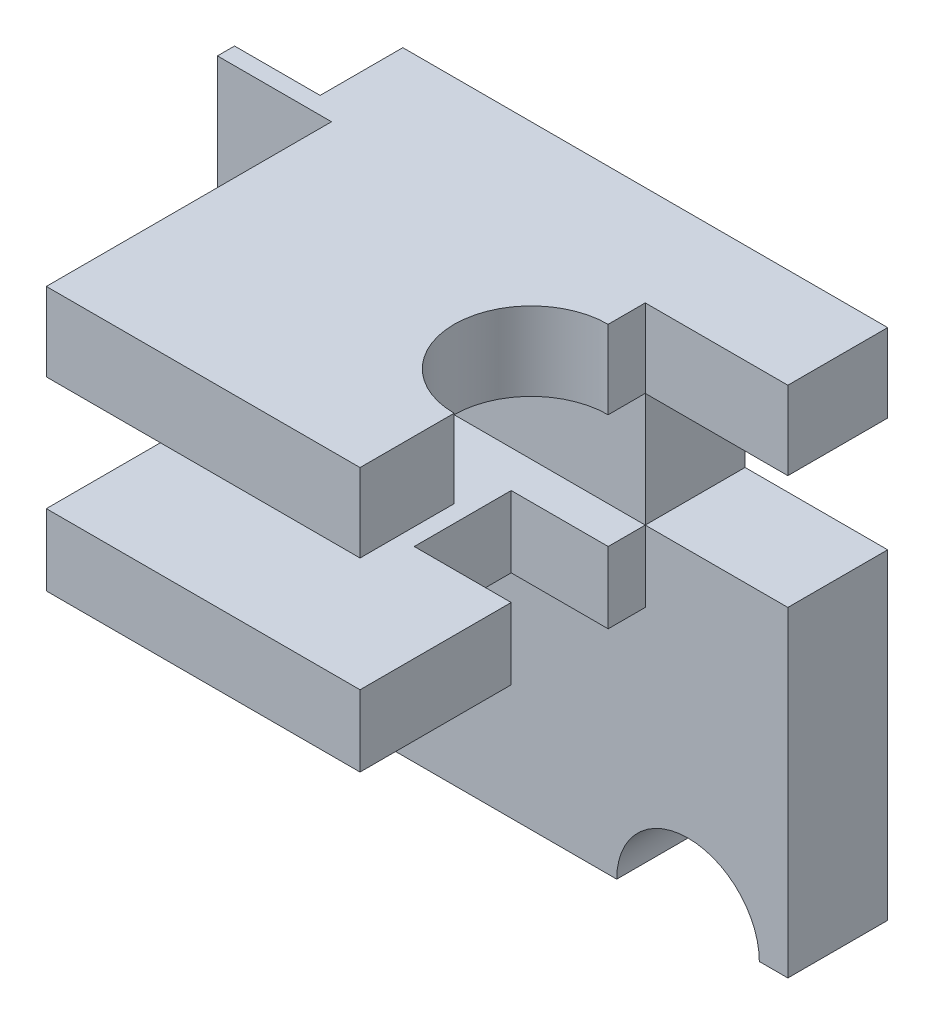
SolidWorks part; units mm, degrees
ref_plane "Спереди" through (0, 0, 0) normal (0, 0, 1) x (1, 0, 0)
ref_plane "Сверху" through (0, 0, 0) normal (0, 1, 0) x (1, 0, 0)
ref_plane "Справа" through (0, 0, 0) normal (1, 0, 0) x (0, 0, -1)
sketch "Эскиз1" plane through (0, 0, 0) normal (0, 0, 1) x (1, 0, 0)
  line L0 (40, -90) -> (90, -90)
  line L1 (-100, -90) -> (100, -90)
  line L2 (-100, -90) -> (-100, 90)
  line L3 (-100, 90) -> (100, 90)
  line L4 (100, -90) -> (100, 90)
  line L5 (-100, -90) -> (100, 90) construction
  line L6 (-100, 90) -> (100, -90) construction
  line L7 (100, 62.5253) -> (50, 62.5253)
  line L8 (100, 62.5253) -> (100, 22.5253)
  line L9 (100, 22.5253) -> (50, 22.5253)
  line L10 (50, 62.5253) -> (50, 22.5253)
  arc A0 (40, -90) -> (90, -90) centre (65, -90) cw
  point P0 (0, 0)
  dimension "D6" = 25
  dimension "D1" = 200
  dimension "D2" = 180
  dimension "D3" = 50
  dimension "D4" = 40
  dimension "D5" = 22.5253
  dimension "D7" = 35
extrude "Бобышка-Вытянуть3" add sketch "Эскиз1" along normal blind 35 contours L2 L1 L4 L3
extrude "Вырез-Вытянуть2" cut sketch "Эскиз1<3>" along normal through all contours A0 L0 | L9 L10 L7 L8 region at (65, -79.3897, 0)
sketch "Эскиз1<3>" plane through (0, 0, 0) normal (0, 0, 1) x (1, 0, 0) same geometry as "Эскиз1"
sketch "Эскиз4" plane through (0, 90, 0) normal (0, 1, 0) x (1, 0, 0)
  line L0 (-100, -35) -> (100, -35) construction
  line L1 (50, -35) -> (-60, -35)
  line L2 (50, -35) -> (50, -135)
  line L3 (50, -135) -> (-60, -135)
  line L4 (-60, -35) -> (-60, -135)
  line L5 (100, -35) -> (100, 0) construction
  dimension "D1" = 50
  dimension "D2" = 110
  dimension "D3" = 100
extrude "Бобышка-Вытянуть4" add sketch "Эскиз4" against normal up to surface (27.4747 mm away) contours L2 L1 L4 L3 up to face at (75, 62.5253, 17.5)
sketch "Эскиз5" plane through (0, 90, 0) normal (0, 1, 0) x (1, 0, 0)
sketch "Эскиз6" plane through (0, 90, 0) normal (0, 1, 0) x (1, 0, 0)
extrude "Бобышка-Вытянуть5" add sketch "Эскиз4<4>" against normal blind 25 from surface starting at face at (75, 22.5253, 17.5)
sketch "Эскиз4<4>" plane through (0, 90, 0) normal (0, 1, 0) x (1, 0, 0) same geometry as "Эскиз4"
sketch "Эскиз9" plane through (0, 90, 0) normal (0, 1, 0) x (1, 0, 0)
  line L1 (-100, 0) -> (-70, 0)
  line L2 (-100, 0) -> (-100, -29)
  line L3 (-100, -29) -> (-70, -29)
  line L4 (-70, 0) -> (-70, -29)
  dimension "D1" = 29
  dimension "D2" = 30
extrude "Вырез-Вытянуть5" cut sketch "Эскиз9" against normal through all
sketch "Эскиз10" plane through (0, 90, 0) normal (0, 1, 0) x (1, 0, 0)
  line L0 (50, -35) -> (50, -135) construction
  line L1 (50, -35) -> (100, -35) construction
  line L2 (50, -48) -> (50, -102)
  arc A0 (50, -48) -> (50, -102) centre (50, -75) ccw
  dimension "D1" = 13
  dimension "D2" = 27
extrude "Вырез-Вытянуть6" cut sketch "Эскиз10" against normal up to surface (27.4747 mm away) up to face at (75, 62.5253, 17.5)
sketch "Эскиз11" plane through (0, -2.4747, 0) normal (0, -1, 0) x (1, 0, 0)
  line L0 (50, 35) -> (50, 135) construction
  line L1 (50, 48) -> (16, 48)
  line L2 (50, 48) -> (50, 82)
  line L3 (50, 82) -> (16, 82)
  line L4 (16, 48) -> (16, 82)
  line L5 (-60, 35) -> (50, 35) construction
  dimension "D1" = 13
  dimension "D2" = 34
  dimension "D3" = 34
extrude "Вырез-Вытянуть7" cut sketch "Эскиз11" against normal up to surface (25 mm away) up to face at (75, 22.5253, 17.5)
